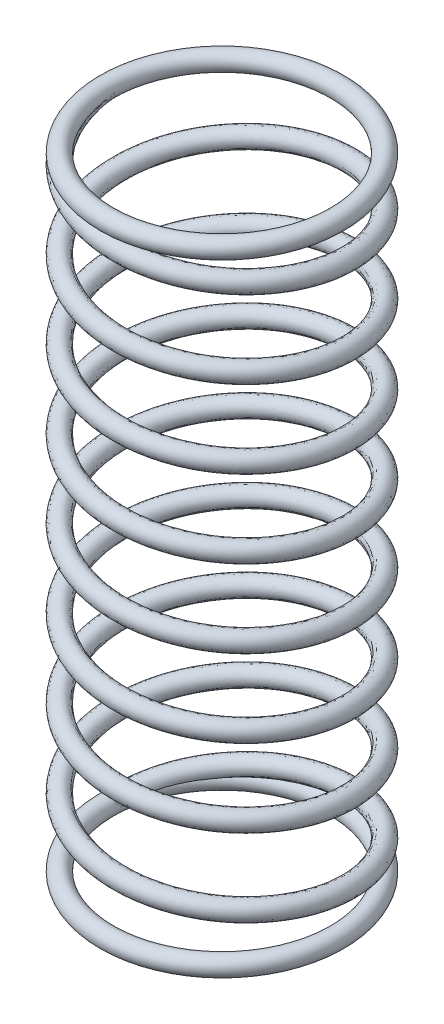
SolidWorks part; units mm, degrees
note: '?' marks a value the reader was unsure of.
ref_plane "Plan de face" through (0, 0, 0) normal (0, 0, 1) x (1, 0, 0)
ref_plane "Plan de dessus" through (0, 0, 0) normal (0, 1, 0) x (1, 0, 0)
ref_plane "Plan de droite" through (0, 0, 0) normal (1, 0, 0) x (0, 0, -1)
sketch "Esquisse1" plane through (0, 0, 0) normal (0, 1, 0) x (1, 0, 0)
  circle A0 centre (0, 0) radius 3.7
  dimension "D1" = 7.4
sketch "Esquisse16" plane through (0, 0, 0) normal (0, 1, 0) x (1, 0, 0)
  circle A2 centre (0, 0) radius 3.7
  circle A3 centre (0, 0) radius 3.7 construction
sweep "Balayage4" add path "Esquisse16" circular profile diameter 0.6 parameters "D3"=0.6
sketch "Esquisse59" plane through (0, 0, 0) normal (0, 1, 0) x (1, 0, 0)
  circle A0 centre (0, 0) radius 3.7
  circle A1 centre (0, 0) radius 3.7 construction
curve "Hélice/Spirale2" pitch 2.5 height 20 turns 8
sweep "Balayage5" add path "Hélice/Spirale2" circular profile diameter 0.6 parameters "D3"=0.6
ref_plane "Plan1" through (0, 20, 0) normal (0, 1, 0) x (1, 0, 0)
sketch "Esquisse68" plane through (0, 20, 0) normal (0, 1, 0) x (1, 0, 0)
  circle A0 centre (0, 0) radius 3.7
  circle A1 centre (0, 0) radius 3.7 construction
sweep "Balayage8" add path "Esquisse68" circular profile diameter 0.6 parameters "D3"=0.6
ref_axis "Axe1" through (0, 26.58, 0) along (0, -1, 0)?
equation "\"D1@Esquisse1\"=\"outer_diameter\"-\"wire_diameter\""
equation "\"wire_diameter\"= 0.6"
equation "\"D3@Balayage4\"=\"wire_diameter\""
equation "\"D3@Balayage5\"=\"wire_diameter\""
equation "\"D3@Balayage8\"=\"wire_diameter\""
equation "\"outer_diameter\"=8"
